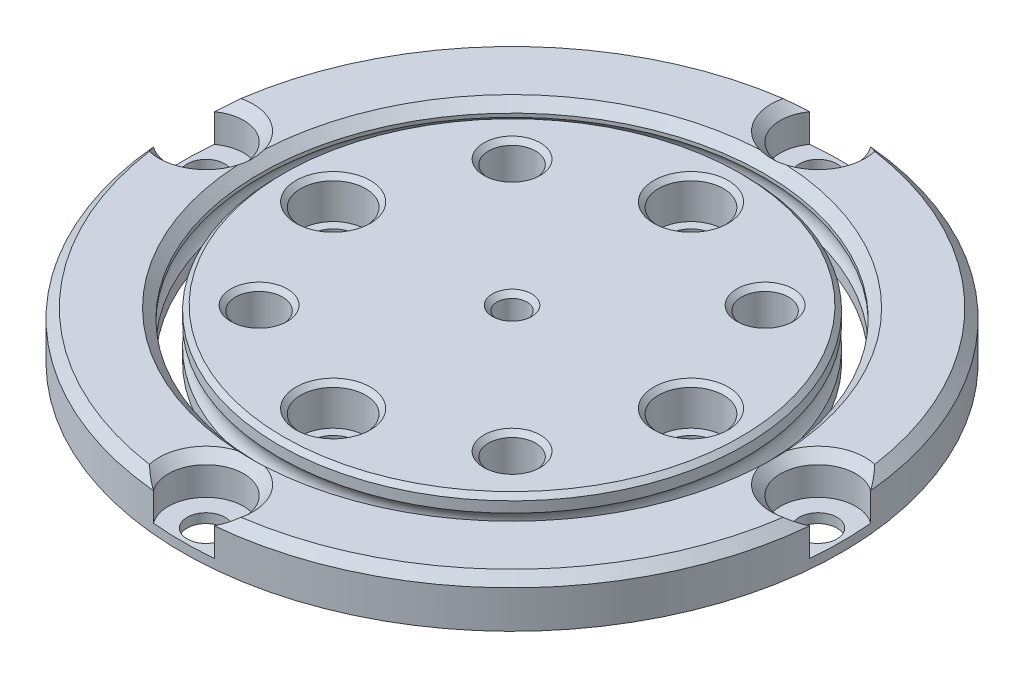
SolidWorks part; units mm, degrees
ref_plane "Front Plane" through (0, 0, 0) normal (0, 0, 1) x (1, 0, 0)
ref_plane "Top Plane" through (0, 0, 0) normal (0, 1, 0) x (1, 0, 0)
ref_plane "Right Plane" through (0, 0, 0) normal (1, 0, 0) x (0, 0, -1)
sketch "Sketch1" plane through (0, 0, 0) normal (0, 1, 0) x (1, 0, 0)
  line L0 (0, 0) -> (0, 19) construction
  circle A1 centre (0, 19) radius 8.5 construction
  circle A2 centre (19, 0) radius 3
  circle A3 centre (19, 0) radius 1.5313
  circle A5 centre (0, 19) radius 10 construction
  circle A10 centre (0, 19) radius 3
  circle A12 centre (0, -19) radius 3
  circle A14 centre (0, 19) radius 1.5313
  circle A17 centre (0, -19) radius 1.5313
  circle A18 centre (-19, 0) radius 3
  circle A19 centre (-19, 0) radius 1.5313
  point P13 (0, 0)
  point P24 (0, 0)
  point P26 (0, 0)
  point P30 (0, 0)
  dimension "D5" = 17
  dimension "D7" = 6
  dimension "D8" = 3.0625
  dimension "D2" = 19
  dimension "D3" = 19
  dimension "D6" = 19
sketch "Sketch2" plane through (0, 0, 0) normal (0, 1, 0) x (-1, 0, 0)
  line L0 (0, 0) -> (-13.435, 13.435) construction
  circle A0 centre (0, 0) radius 23.75
  circle A2 centre (0, 0) radius 19 construction
  circle A3 centre (-13.435, 13.435) radius 2.5
  circle A4 centre (13.435, 13.435) radius 2.5
  circle A8 centre (0, 0) radius 1.5875
  circle A9 centre (13.435, -13.435) radius 2.5
  circle A10 centre (0, 19) radius 2.5
  circle A11 centre (19, 0) radius 2.5
  circle A12 centre (0, -19) radius 2.5
  circle A13 centre (-19, 0) radius 2.5
  circle A14 centre (-13.435, -13.435) radius 2.5
  point P19 (0, 0)
  point P27 (0, 0)
  dimension "D1" = 3.175
  dimension "D2" = 47.5
  dimension "D4" = 5
  dimension "D6" = 5
  dimension "D3" = 4
  dimension "D5" = 4
extrude "Boss-Extrude2" add sketch "Sketch2" against normal blind 5 contours A0 A11 A10 A8 region at (23.0782, 0, 0)
sketch "Sketch3" plane through (0, 0, 0) normal (0, 1, 0) x (1, 0, 0)
  circle A0 centre (0, 19) radius 3.45
  circle A1 centre (19, 0) radius 3.45
  circle A2 centre (0, -19) radius 3.45
  circle A3 centre (-19, 0) radius 3.45
  point P12 (0, 0)
  dimension "D1" = 6.9
  dimension "D2" = 4
extrude "Cut-Extrude1" cut sketch "Sketch3" against normal blind 4
sketch "Sketch4" plane through (0, 0, 0) normal (0, 0, 1) x (1, 0, 0)
  line L0 (-23.75, -5) -> (-23.75, 0) construction
  line L1 (-23.75, 0) -> (-23.75, -5) construction
  line L2 (-23.75, 0) -> (-24.75, 0) construction
  line L3 (-27.75, 0) -> (-27.75, -5) construction
  line L4 (-27.75, -5) -> (-25.75, -5) construction
  line L5 (-23.75, -5) -> (-24.75, -5) construction
  line L6 (-25.75, -5) -> (-25.75, 0) construction
  line L7 (-25.75, -1.95) -> (-25.75, 0) construction
  line L8 (-24.75, 0) -> (-23.75, 0)
  line L11 (-23.75, -2.5) -> (-17.0406, -2.5) construction
  line L12 (-23.75, -5) -> (-24.75, -5) construction
  line L14 (-24.75, -5) -> (-23.75, -5)
  line L15 (-25.75, -3.05) -> (-25.75, -5) construction
  line L16 (-24.75, 0) -> (-24.75, -1.382)
  line L17 (-24.75, -5) -> (-24.75, -3.618)
  line L18 (-25.75, 0) -> (-27.75, 0) construction
  line L19 (-24.75, -5) -> (-23.75, -5) construction
  line L20 (-25.75, -5) -> (-27.75, -5) construction
  line L21 (-26.75, -5) -> (-26.75, -3.618)
  line L22 (-26.75, 0) -> (-26.75, -1.382)
  line L23 (-26.75, 0) -> (-35, 0)
  line L24 (-35, 0) -> (-35, -5)
  line L25 (-35, -5) -> (-26.75, -5)
  line L26 (23.75, -2.5) -> (-23.75, -2.5) construction
  line L27 (23.75, 0) -> (-23.75, 0) construction
  line L28 (23.75, -5) -> (23.75, 0) construction
  line L29 (0, -2.5) -> (0, 0) construction
  line L30 (-23.75, -2.5) -> (-35, -2.5) construction
  line L31 (-23.75, 0) -> (-23.75, -5)
  arc A5 (-26.75, -1.382) -> (-26.75, -3.618) centre (-25.75, -2.5) ccw
  arc A6 (-24.75, -3.618) -> (-24.75, -1.382) centre (-25.75, -2.5) ccw
  dimension "D1" = 1.5
  dimension "D3" = 1
  dimension "D2" = 2
  dimension "D4" = 35
revolve "Revolve1" add sketch "Sketch4" angle 360 about L29
sketch "Sketch5" plane through (0, 0, 0) normal (0, 1, 0) x (1, 0, 0)
  circle A0 centre (0, 0) radius 32.5 construction
  circle A1 centre (0, 32.5) radius 2
  circle A2 centre (32.5, 0) radius 2
  circle A3 centre (0, -32.5) radius 2
  circle A4 centre (-32.5, 0) radius 2
  point P14 (0, 0)
  dimension "D1" = 4
extrude "Cut-Extrude2" cut sketch "Sketch5" against normal blind 10
sketch "Sketch6" plane through (0, 0, 0) normal (0, 1, 0) x (1, 0, 0)
  circle A0 centre (0, -32.5) radius 4
  circle A1 centre (-32.5, 0) radius 4
  circle A2 centre (0, 32.5) radius 4
  circle A3 centre (32.5, 0) radius 4
  point P12 (0, 0)
  dimension "D1" = 8
extrude "Cut-Extrude3" cut sketch "Sketch6" against normal blind 4
chamfer "Chamfer2" distance 1 angle 45 9 edges at (0, 0, -26.75) (-28.5, 0, 0) (-24.7487, 0, -24.7487) (0, 0, -28.5) (24.7487, 0, -24.7487) (28.5, 0, 0) (24.7487, 0, 24.7487) (0, 0, 28.5) (-24.7487, 0, 24.7487)
sketch "Sketch7" plane through (0, 0, 0) normal (0, 1, 0) x (1, 0, 0)
  circle A0 centre (0, 0) radius 24.75
  circle A1 centre (13.435, 13.435) radius 2.5
  circle A2 centre (13.435, 13.435) radius 2.5
  circle A3 centre (-13.435, 13.435) radius 2.5
  circle A4 centre (-13.435, 13.435) radius 2.5
  circle A5 centre (0, 0) radius 1.5875
  circle A6 centre (0, 0) radius 1.5875
  circle A7 centre (-13.435, -13.435) radius 2.5
  circle A8 centre (-13.435, -13.435) radius 2.5
  circle A9 centre (13.435, -13.435) radius 2.5
  circle A10 centre (13.435, -13.435) radius 2.5
  circle A11 centre (-19, 0) radius 3.45
  circle A12 centre (-19, 0) radius 3.45
  circle A13 centre (0, -19) radius 3.45
  circle A14 centre (0, -19) radius 3.45
  circle A15 centre (19, 0) radius 3.45
  circle A16 centre (19, 0) radius 3.45
  circle A17 centre (0, 19) radius 3.45
  circle A18 centre (0, 19) radius 3.45
  dimension "D1" = 0
  dimension "D2" = 0
  dimension "D3" = 0
  dimension "D4" = 0
  dimension "D5" = 0
  dimension "D6" = 0
  dimension "D7" = 0
  dimension "D8" = 0
  dimension "D9" = 0
extrude "Boss-Extrude3" add sketch "Sketch7" along normal blind 0.25
chamfer "Chamfer3" distance 0.5 angle 45 10 edges at (0, 0.25, -15.55) (0, 0.25, 22.45) (13.435, 0.25, 15.935) (0, 0.25, 1.5875) (13.435, 0.25, -10.935) (0, 0.25, 24.75) (-13.435, 0.25, -10.935) (-13.435, 0.25, 15.935) (-19, 0.25, 3.45) (19, 0.25, 3.45)
